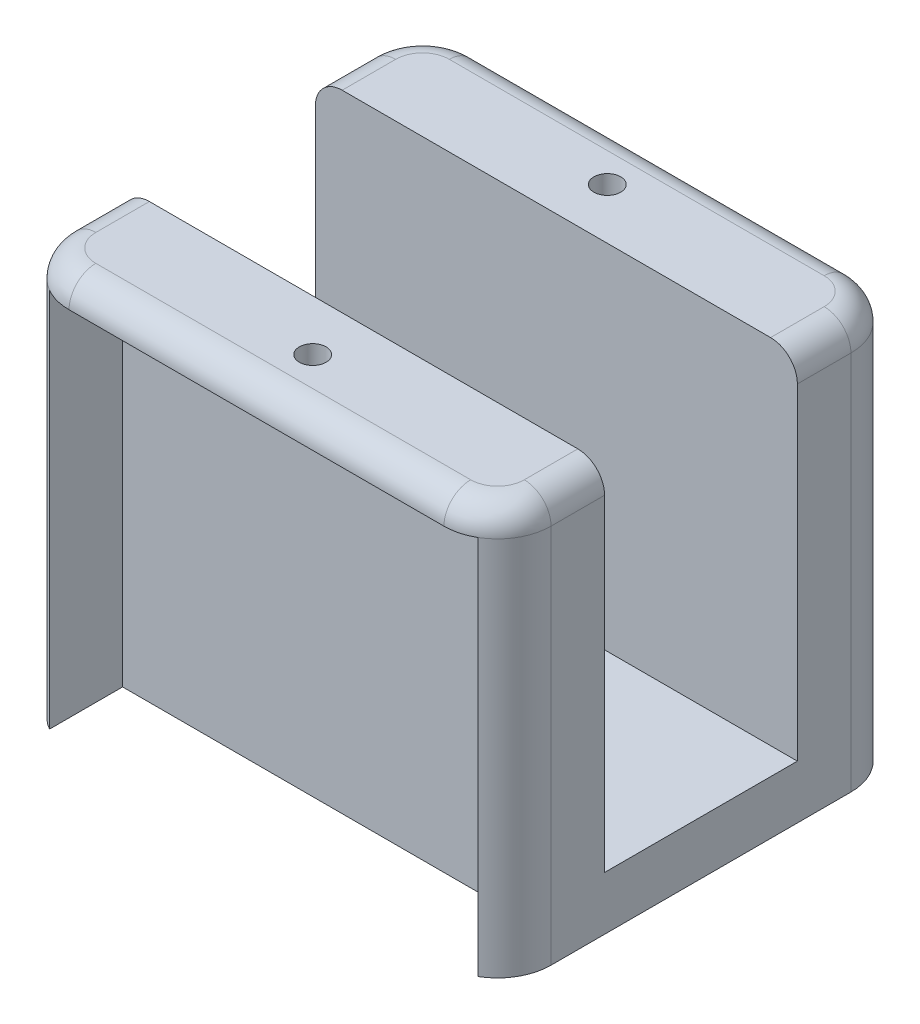
SolidWorks part; units mm, degrees
material "1.4105 (X6CrMoS17)"
ref_plane "前视基准面" through (0, 0, 0) normal (0, 0, 1) x (1, 0, 0)
ref_plane "上视基准面" through (0, 0, 0) normal (0, 1, 0) x (1, 0, 0)
ref_plane "右视基准面" through (0, 0, 0) normal (1, 0, 0) x (0, 0, -1)
sketch "Sketch1" plane through (0, 0, 0) normal (0, 1, 0) x (1, 0, 0)
  line L1 (-45, 33) -> (45, 33)
  line L2 (-45, 33) -> (-45, -33)
  line L3 (-45, -33) -> (45, -33)
  line L4 (45, 33) -> (45, -33)
  line L5 (-45, 33) -> (45, -33) construction
  line L6 (-45, -33) -> (45, 33) construction
  point P1 (0, 0)
extrude "Boss-Extrude1" add sketch "Sketch1" along normal blind 76
sketch "Sketch2" plane through (0, 76, 0) normal (0, 1, 0) x (1, 0, 0)
  line L0 (45, -33) -> (45, 33) construction
  line L1 (-45, 18) -> (45, 18)
  line L2 (-45, 18) -> (-45, -18)
  line L3 (-45, -18) -> (45, -18)
  line L4 (45, 18) -> (45, -18)
  line L5 (-45, 18) -> (45, -18) construction
  line L6 (-45, -18) -> (45, 18) construction
  point P0 (0, 0)
extrude "Cut-Extrude1" cut sketch "Sketch2" against normal blind 66
sketch "Sketch3" plane through (0, 0, -33) normal (0, 0, -1) x (-1, 0, 0)
  line L1 (-45, 76) -> (45, 76)
  line L2 (-45, 76) -> (-45, 0)
  line L3 (-45, 0) -> (45, 0)
  line L4 (45, 76) -> (45, 0)
extrude "Boss-Extrude4" add sketch "Sketch3" along normal blind 5
sketch "Sketch11" plane through (0, 0, 33) normal (0, 0, 1) x (1, 0, 0)
  line L1 (-45, 76) -> (45, 76)
  line L2 (-45, 76) -> (-45, 0)
  line L3 (-45, 0) -> (45, 0)
  line L4 (45, 76) -> (45, 0)
extrude "Boss-Extrude5" add sketch "Sketch11" along normal blind 5
sketch "Sketch12" plane through (0, 0, 38) normal (0, 0, 1) x (1, 0, 0)
  line L0 (-45, 0) -> (45, 0) construction
  line L1 (-40, 71) -> (40, 71)
  line L2 (-40, 71) -> (-40, 0)
  line L3 (-40, 0) -> (40, 0)
  line L4 (40, 71) -> (40, 0)
extrude "Cut-Extrude9" cut sketch "Sketch12" against normal blind 15
sketch "Sketch13" plane through (0, 0, -38) normal (0, 0, -1) x (-1, 0, 0)
  line L0 (-45, 0) -> (45, 0) construction
  line L1 (-40, 71) -> (40, 71)
  line L2 (-40, 71) -> (-40, 0)
  line L3 (-40, 0) -> (40, 0)
  line L4 (40, 71) -> (40, 0)
extrude "Cut-Extrude10" cut sketch "Sketch13" against normal blind 15
sketch "Sketch14" plane through (0, 76, 0) normal (0, 1, 0) x (1, 0, 0)
  circle A0 centre (0, 27.5) radius 2.5
extrude "Cut-Extrude11" cut sketch "Sketch14" against normal blind 5
sketch "Sketch15" plane through (0, 76, 0) normal (0, 1, 0) x (1, 0, 0)
  circle A0 centre (0, -27.5) radius 2.5
extrude "Cut-Extrude12" cut sketch "Sketch15" against normal blind 5
fillet "Fillet1" radius 10 4 edges at (-45, 38, -38) (45, 38, -38) (-45, 38, 38) (45, 38, 38)
fillet "Fillet2" radius 5 10 edges at (45, 76, -23) (42.0711, 76, -35.0711) (-42.0711, 76, -35.0711) (45, 76, 23) (42.0711, 76, 35.0711) (0, 76, 38) (-42.0711, 76, 35.0711) (0, 76, -38) (-45, 76, -23) (-45, 76, 23)
